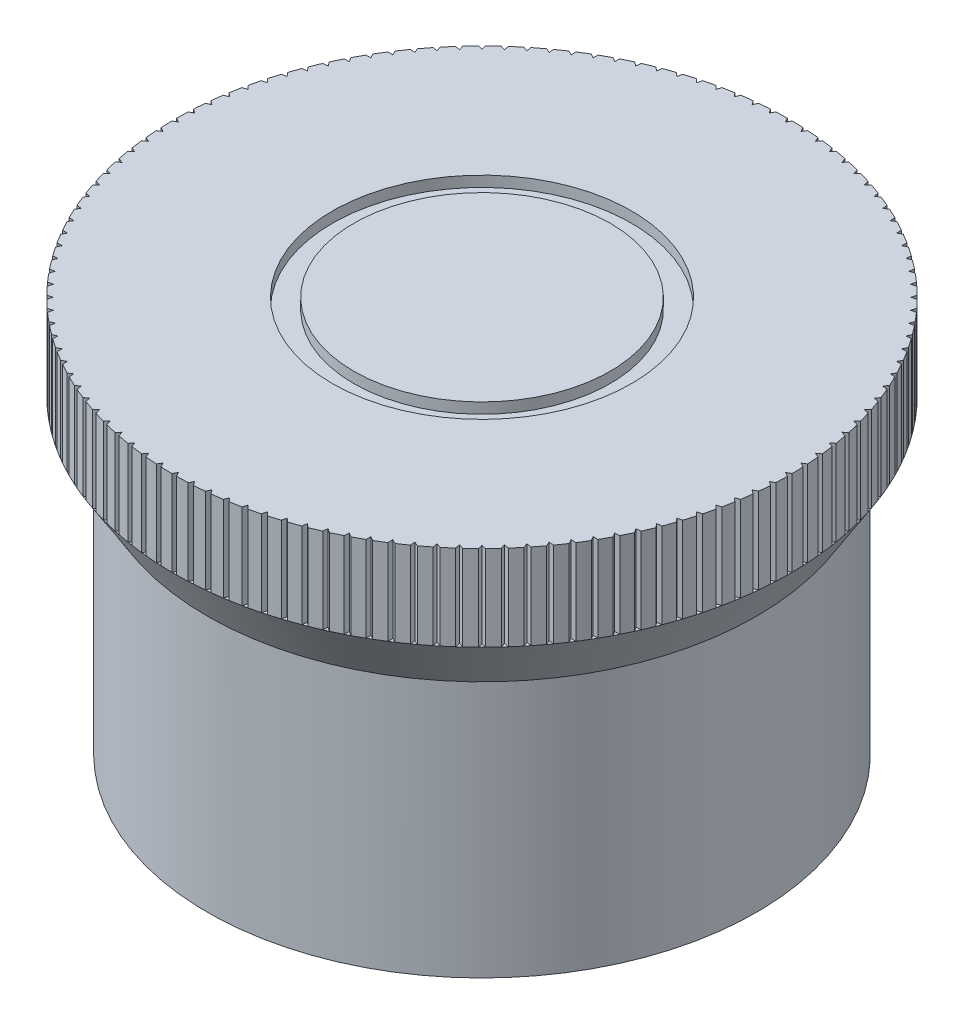
SolidWorks part; units mm, degrees
ref_plane "正面" through (0, 0, 0) normal (0, 0, 1) x (1, 0, 0)
ref_plane "平面" through (0, 0, 0) normal (0, 1, 0) x (1, 0, 0)
ref_plane "右側面" through (0, 0, 0) normal (1, 0, 0) x (0, 0, -1)
sketch "ｽｹｯﾁ1" plane through (0, 0, 0) normal (0, 1, 0) x (1, 0, 0)
  circle A0 centre (0, 0) radius 14.4
  dimension "D1" = 28.8
extrude "ﾎﾞｽ - 押し出し1" add sketch "ｽｹｯﾁ1" along normal blind 4
sketch "ｽｹｯﾁ3" plane through (0, 4, 0) normal (0, 1, 0) x (1, 0, 0)
  line L0 (-14.3995, 0.1152) -> (-14.2, 0)
  line L1 (-14.2, 0) -> (-14.3995, -0.1152)
  line L2 (0, 0) -> (-50000, 0) construction
  circle A1 centre (0, 0) radius 14.4 construction
  arc A2 (-14.3995, 0.1152) -> (-14.3995, -0.1152) centre (0, 0) ccw
  dimension "D1" = 30
  dimension "D2" = 14.2
extrude "ｶｯﾄ - 押し出し1" cut sketch "ｽｹｯﾁ3" against normal through all
pattern_circular "円形ﾊﾟﾀｰﾝ1" count 120 over 360 about axis through (0, 4, 0) along (0, -1, 0) of "ｶｯﾄ - 押し出し1"
sketch "ｽｹｯﾁ8" plane through (0, 4, 0) normal (0, 1, 0) x (1, 0, 0)
  circle A0 centre (0, 0) radius 7
  circle A1 centre (0, 0) radius 6
  dimension "D1" = 12
  dimension "D2" = 14
extrude "ｶｯﾄ - 押し出し2" cut sketch "ｽｹｯﾁ8" against normal blind 0.5
ref_plane "平面2" through (0, -2.5, 0) normal (0, 1, 0) x (-1, 0, 0)
sketch "ｽｹｯﾁ9" plane through (0, -2.5, 0) normal (0, 1, 0) x (-1, 0, 0)
  circle A0 centre (0, 0) radius 12.85
  dimension "D1" = 25.7
sketch "ｽｹｯﾁ10" plane through (0, 0, 0) normal (0, -1, 0) x (1, 0, 0)
  circle A0 centre (0, 0) radius 14.4
loft "ﾛﾌﾄ2" add profiles "ｽｹｯﾁ10", "ｽｹｯﾁ9" connector at (-13.9039, 0, 3.7474) connector at (-12.472, -2.5, 3.0939)
sketch "ｽｹｯﾁ11" plane through (0, -2.5, 0) normal (0, -1, 0) x (1, 0, 0)
  circle A0 centre (0, 0) radius 12.85
  dimension "D1" = 25.7
extrude "ﾎﾞｽ - 押し出し2" add sketch "ｽｹｯﾁ11" along normal blind 12
